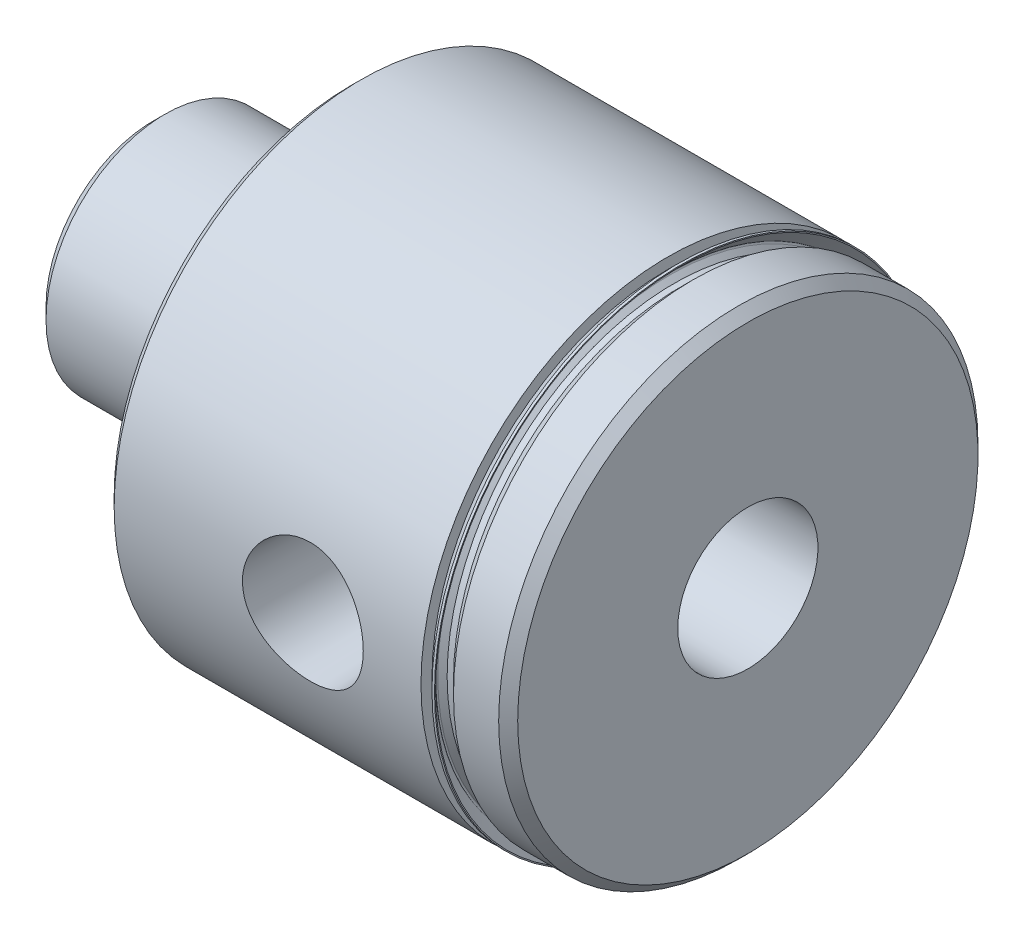
SolidWorks part; units mm, degrees
material "6061-T6 (SS)"
ref_plane "Front Plane" through (0, 0, 0) normal (0, 0, 1) x (1, 0, 0)
ref_plane "Top Plane" through (0, 0, 0) normal (0, 1, 0) x (1, 0, 0)
ref_plane "Right Plane" through (0, 0, 0) normal (1, 0, 0) x (0, 0, -1)
sketch "Sketch1" plane through (0, 0, 0) normal (0, 0, 1) x (1, 0, 0)
  line L0 (0, 0) -> (0, 8.589)
  line L1 (0, 8.589) -> (0.936, 9.525)
  line L2 (0.936, 9.525) -> (9.31, 9.525)
  line L3 (9.31, 9.525) -> (10.2623, 8.6108)
  line L4 (11.0363, 8.2995) -> (12.3698, 8.2995)
  line L5 (13.4874, 9.417) -> (13.4874, 9.4932)
  line L6 (13.4874, 9.4932) -> (15.875, 9.4932)
  line L7 (15.875, 9.4932) -> (15.875, 0)
  line L8 (15.875, 0) -> (0, 0)
  line L9 (15.875, 0) -> (0, 0) construction
  arc A0 (10.2623, 8.6108) -> (11.0363, 8.2995) centre (11.0363, 9.417) ccw
  arc A1 (12.3698, 8.2995) -> (13.4874, 9.417) centre (12.3698, 9.4171) ccw
revolve "Revolve1" add sketch "Sketch1" angle 360 about L9 reverse direction yes
cosmetic thread "Cosmetic Thread1" parameters "D1"=10.246, "D2"=17.178
sketch "Sketch2" plane through (0, 0, 0) normal (0, 0, 1) x (1, 0, 0)
  line L0 (15.875, 0) -> (15.875, 19.0055)
  line L1 (15.875, 19.0055) -> (16.637, 19.7676)
  line L2 (16.637, 19.7676) -> (41.2115, 19.7676)
  line L3 (41.2115, 19.7676) -> (41.2115, 18.1801)
  line L4 (41.2115, 18.1801) -> (42.2275, 18.1801)
  line L5 (42.2275, 18.1801) -> (43.2435, 19.196)
  line L6 (43.2435, 19.196) -> (46.863, 19.196)
  line L7 (46.863, 19.196) -> (47.625, 18.434)
  line L8 (47.625, 18.434) -> (47.625, 0)
  line L9 (47.625, 0) -> (15.875, 0)
  line L10 (47.625, 0) -> (15.875, 0) construction
revolve "Revolve2" add sketch "Sketch2" angle 360 about L10 reverse direction yes
sketch "Sketch3" plane through (0, 0, 0) normal (0, 0, 1) x (1, 0, 0)
  line L0 (0, 0) -> (0, 6.3754)
  line L1 (0, 6.3754) -> (0.762, 5.6134)
  line L2 (0.762, 5.6134) -> (47.625, 5.6134)
  line L3 (47.625, 5.6134) -> (47.625, 0)
  line L4 (47.625, 0) -> (0, 0)
  line L5 (47.625, 0) -> (0, 0) construction
revolve "Cut-Revolve1" cut sketch "Sketch3" angle 360 about L5 reverse direction yes
ref_plane "Plane1" through (25.527, 0, 0) normal (1, 0, 0) x (0, 0, -1)
ref_plane "Plane2" through (25.527, 0, 0) normal (1, 0, 0) x (0, 0, -1)
ref_plane "Plane3" through (0, 0, 0) normal (0, -0.7071, 0.7071) x (1, 0, 0)
ref_plane "Plane4" through (3.1242, 0, 0) normal (1, 0, 0) x (0, 0, -1)
ref_plane "Plane5" through (41.275, 0, 0) normal (1, 0, 0) x (0, 0, -1)
ref_plane "Plane6" through (15.875, 0, 0) normal (1, 0, 0) x (0, 0, -1)
ref_plane "Plane7" through (41.275, 0, 0) normal (1, 0, 0) x (0, 0, -1)
sketch "Sketch4" plane through (0, 0, 0) normal (0, 1, 0) x (1, 0, 0)
  line L0 (31.75, 0) -> (34.925, 0)
  line L1 (34.925, 0) -> (34.925, -7.7681)
  line L2 (34.925, -7.7681) -> (36.2564, -9.0996)
  line L3 (36.2564, -9.0996) -> (36.5895, -19.7676)
  line L4 (36.5895, -19.7676) -> (31.75, -19.7676)
  line L5 (31.75, -19.7676) -> (31.75, 0)
  line L6 (31.75, -19.7676) -> (31.75, 0) construction
revolve "Cut-Revolve2" cut sketch "Sketch4" angle 360 about L6 reverse direction yes
cosmetic thread "Cosmetic Thread2" parameters "D1"=6.4008, "D2"=10.287
sketch "Sketch5" plane through (0, 0, 0) normal (0, 0, 1) x (1, 0, 0)
  line L0 (41.2115, 18.8883) -> (41.2115, 17.9261)
  line L1 (41.2115, 17.9261) -> (42.2275, 17.9261)
  line L2 (42.2275, 17.9261) -> (42.2275, 18.1801)
  line L3 (42.2275, 18.1801) -> (41.7195, 18.1801)
  line L4 (41.7195, 18.1801) -> (41.3449, 18.5547)
  line L5 (41.3449, 18.7343) -> (42.294, 19.6834)
  line L6 (42.294, 19.6834) -> (42.294, 19.7676)
  line L7 (42.294, 19.7676) -> (42.0908, 19.7676)
  line L8 (42.0908, 19.7676) -> (41.2115, 18.8883)
  line L9 (42.2275, 0) -> (41.2115, 0) construction
  arc A0 (41.3449, 18.5547) -> (41.3449, 18.7343) centre (41.4347, 18.6445) cw
revolve "Revolve3" add sketch "Sketch5" angle 360 about L9 reverse direction yes
ref_plane "Plane8" through (42.2275, 0, 0) normal (1, 0, 0) x (0, 0, -1)
ref_plane "Plane9" through (15.875, 0, 0) normal (1, 0, 0) x (0, 0, -1)
ref_plane "Plane10" through (13.4874, 0, 0) normal (1, 0, 0) x (0, 0, -1)
ref_plane "Plane11" through (0, 22.225, 0) normal (0, 1, 0) x (1, 0, 0)
ref_plane "Plane12" through (0, -22.225, 0) normal (0, 1, 0) x (1, 0, 0)
ref_plane "Plane13" through (15.875, 0, 0) normal (1, 0, 0) x (0, 0, -1)
ref_plane "Plane14" through (0, 0, 0) normal (0, 0, 1) x (1, 0, 0)
ref_plane "Plane15" through (0, 0, 0) normal (0, 1, 0) x (1, 0, 0)
ref_plane "Plane16" through (0, 0, 0) normal (0, 1, 0) x (1, 0, 0)
ref_plane "Plane17" through (0, 14.2875, 0) normal (0, 1, 0) x (1, 0, 0)
ref_plane "Plane18" through (0, 0, 0) normal (1, 0, 0) x (0, 0, -1)
ref_plane "dp1 XY" through (0, 0, 0) normal (0, 0, 1) x (1, 0, 0)
ref_plane "dp1 XZ" through (0, 9.4932, 0) normal (0, -1, 0) x (-1, 0, 0)
ref_plane "dp1 YZ" through (15.875, 0, 0) normal (1, 0, 0) x (0, 0, -1)
ref_axis "dp1 X" through (-80.9, 9.4932, 0) along (1, 0, 0)
ref_axis "dp1 Y" through (15.875, -50, 0) along (0, 1, 0)
ref_axis "dp1 Z" through (15.875, 9.4932, 80.9) along (0, 0, -1)
sketch3d "dp1"
  point P0 (15.875, 9.4932, 0)
ref_plane "dp2 XY" through (0, 0, 0) normal (0, 0, 1) x (1, 0, 0)
ref_plane "dp2 XZ" through (0, -9.4932, 0) normal (0, -1, 0) x (-1, 0, 0)
ref_plane "dp2 YZ" through (15.875, 0, 0) normal (1, 0, 0) x (0, 0, -1)
ref_axis "dp2 X" through (-80.9, -9.4932, 0) along (1, 0, 0)
ref_axis "dp2 Y" through (15.875, -50, 0) along (0, 1, 0)
ref_axis "dp2 Z" through (15.875, -9.4932, 80.9) along (0, 0, -1)
sketch3d "dp2"
  point P0 (15.875, -9.4932, 0)
ref_plane "port XY" through (0, 0, 0) normal (0, 0, 1) x (1, 0, 0)
ref_plane "port XZ" through (0, 0, 0) normal (0, -1, 0) x (-1, 0, 0)
ref_plane "port YZ" through (31.75, 0, 0) normal (1, 0, 0) x (0, 0, -1)
ref_axis "port X" through (-80.9, 0, 0) along (1, 0, 0)
ref_axis "port Y" through (31.75, -50, 0) along (0, 1, 0)
ref_axis "port Z" through (31.75, 0, 80.9) along (0, 0, -1)
sketch3d "port"
  point P0 (31.75, 0, 0)
ref_plane "rod_guide XY" through (0, 0, 0) normal (1, 0, 0) x (0, 0, -1)
ref_plane "rod_guide XZ" through (0, 0, 0) normal (0, -1, 0) x (-1, 0, 0)
ref_plane "rod_guide YZ" through (0, 0, 0) normal (0, 0, -1) x (-1, 0, 0)
ref_axis "rod_guide X" through (0, 0, 80.9) along (0, 0, -1)
ref_axis "rod_guide Y" through (0, -50, 0) along (0, 1, 0)
ref_axis "rod_guide Z" through (80.9, 0, 0) along (-1, 0, 0)
sketch3d "rod_guide"
  point P0 (0, 0, 0)
ref_plane "s1 XY" through (0, 0, 0) normal (0, 0, 1) x (1, 0, 0)
ref_plane "s1 XZ" through (0, 0, 0) normal (0, -1, 0) x (-1, 0, 0)
ref_plane "s1 YZ" through (13.4874, 0, 0) normal (1, 0, 0) x (0, 0, -1)
ref_axis "s1 X" through (-80.9, 0, 0) along (1, 0, 0)
ref_axis "s1 Y" through (13.4874, -50, 0) along (0, 1, 0)
ref_axis "s1 Z" through (13.4874, 0, 80.9) along (0, 0, -1)
sketch3d "s1"
  point P0 (13.4874, 0, 0)
ref_plane "s2 XY" through (0, 0, 0) normal (0, 0, 1) x (1, 0, 0)
ref_plane "s2 XZ" through (0, 0, 0) normal (0, -1, 0) x (-1, 0, 0)
ref_plane "s2 YZ" through (15.875, 0, 0) normal (1, 0, 0) x (0, 0, -1)
ref_axis "s2 X" through (-80.9, 0, 0) along (1, 0, 0)
ref_axis "s2 Y" through (15.875, -50, 0) along (0, 1, 0)
ref_axis "s2 Z" through (15.875, 0, 80.9) along (0, 0, -1)
sketch3d "s2"
  point P0 (15.875, 0, 0)
ref_plane "t1 XY" through (15.875, 0, 0) normal (1, 0, 0) x (0, 0, -1)
ref_plane "t1 XZ" through (0, 0, 0) normal (0, -1, 0) x (-1, 0, 0)
ref_plane "t1 YZ" through (0, 0, 0) normal (0, 0, -1) x (-1, 0, 0)
ref_axis "t1 X" through (15.875, 0, 80.9) along (0, 0, -1)
ref_axis "t1 Y" through (15.875, -50, 0) along (0, 1, 0)
ref_axis "t1 Z" through (80.9, 0, 0) along (-1, 0, 0)
sketch3d "t1"
  point P0 (15.875, 0, 0)
ref_plane "t111 XY" through (15.875, 0, 0) normal (1, 0, 0) x (0, 0, -1)
ref_plane "t111 XZ" through (0, 0, 0) normal (0, -1, 0) x (-1, 0, 0)
ref_plane "t111 YZ" through (0, 0, 0) normal (0, 0, -1) x (-1, 0, 0)
ref_axis "t111 X" through (15.875, 0, 80.9) along (0, 0, -1)
ref_axis "t111 Y" through (15.875, -50, 0) along (0, 1, 0)
ref_axis "t111 Z" through (80.9, 0, 0) along (-1, 0, 0)
sketch3d "t111"
  point P0 (15.875, 0, 0)
ref_plane "to_foot_bracket XY" through (15.875, 0, 0) normal (1, 0, 0) x (0, 0, -1)
ref_plane "to_foot_bracket XZ" through (0, 0, 0) normal (0, -1, 0) x (-1, 0, 0)
ref_plane "to_foot_bracket YZ" through (0, 0, 0) normal (0, 0, -1) x (-1, 0, 0)
ref_axis "to_foot_bracket X" through (15.875, 0, 80.9) along (0, 0, -1)
ref_axis "to_foot_bracket Y" through (15.875, -50, 0) along (0, 1, 0)
ref_axis "to_foot_bracket Z" through (80.9, 0, 0) along (-1, 0, 0)
sketch3d "to_foot_bracket"
  point P0 (15.875, 0, 0)
ref_plane "to_nut XY" through (13.4874, 0, 0) normal (1, 0, 0) x (0, 0, -1)
ref_plane "to_nut XZ" through (0, 0, 0) normal (0, -1, 0) x (-1, 0, 0)
ref_plane "to_nut YZ" through (0, 0, 0) normal (0, 0, -1) x (-1, 0, 0)
ref_axis "to_nut X" through (13.4874, 0, 80.9) along (0, 0, -1)
ref_axis "to_nut Y" through (13.4874, -50, 0) along (0, 1, 0)
ref_axis "to_nut Z" through (80.9, 0, 0) along (-1, 0, 0)
sketch3d "to_nut"
  point P0 (13.4874, 0, 0)
ref_plane "to_rod XY" through (0, 0, 0) normal (1, 0, 0) x (0, 0, -1)
ref_plane "to_rod XZ" through (0, 0, 0) normal (0, -1, 0) x (-1, 0, 0)
ref_plane "to_rod YZ" through (0, 0, 0) normal (0, 0, -1) x (-1, 0, 0)
ref_axis "to_rod X" through (0, 0, 80.9) along (0, 0, -1)
ref_axis "to_rod Y" through (0, -50, 0) along (0, 1, 0)
ref_axis "to_rod Z" through (80.9, 0, 0) along (-1, 0, 0)
sketch3d "to_rod"
  point P0 (0, 0, 0)
ref_plane "to_screw XY" through (0, 14.2875, 0) normal (0, 1, 0) x (1, 0, 0)
ref_plane "to_screw XZ" through (0, 0, -10.0711) normal (0, 0, 1) x (1, 0, 0)
ref_plane "to_screw YZ" through (31.75, 0, 0) normal (1, 0, 0) x (0, 0, -1)
ref_axis "to_screw X" through (-80.9, 14.2875, -10.0711) along (1, 0, 0)
ref_axis "to_screw Y" through (31.75, 14.2875, 50) along (0, 0, -1)
ref_axis "to_screw Z" through (31.75, 50, -10.0711) along (0, -1, 0)
sketch3d "to_screw"
  point P0 (31.75, 14.2875, -10.0711)
ref_plane "to_trunnion_brackets XY" through (0, 0, 0) normal (0, 1, 0) x (1, 0, 0)
ref_plane "to_trunnion_brackets XZ" through (0, 0, 0) normal (0, 0, 1) x (1, 0, 0)
ref_plane "to_trunnion_brackets YZ" through (26.9494, 0, 0) normal (1, 0, 0) x (0, 0, -1)
ref_axis "to_trunnion_brackets X" through (-80.9, 0, 0) along (1, 0, 0)
ref_axis "to_trunnion_brackets Y" through (26.9494, 0, 50) along (0, 0, -1)
ref_axis "to_trunnion_brackets Z" through (26.9494, 50, 0) along (0, -1, 0)
sketch3d "to_trunnion_brackets"
  point P0 (26.9494, 0, 0)
ref_plane "to_trunnion_brackets1 XY" through (0, 22.225, 0) normal (0, 1, 0) x (1, 0, 0)
ref_plane "to_trunnion_brackets1 XZ" through (0, 0, 0) normal (0, 0, 1) x (1, 0, 0)
ref_plane "to_trunnion_brackets1 YZ" through (26.9494, 0, 0) normal (1, 0, 0) x (0, 0, -1)
ref_axis "to_trunnion_brackets1 X" through (-80.9, 22.225, 0) along (1, 0, 0)
ref_axis "to_trunnion_brackets1 Y" through (26.9494, 22.225, 50) along (0, 0, -1)
ref_axis "to_trunnion_brackets1 Z" through (26.9494, 50, 0) along (0, -1, 0)
sketch3d "to_trunnion_brackets1"
  point P0 (26.9494, 22.225, 0)
ref_plane "to_trunnion_brackets2 XY" through (0, -22.225, 0) normal (0, 1, 0) x (1, 0, 0)
ref_plane "to_trunnion_brackets2 XZ" through (0, 0, 0) normal (0, 0, 1) x (1, 0, 0)
ref_plane "to_trunnion_brackets2 YZ" through (26.9494, 0, 0) normal (1, 0, 0) x (0, 0, -1)
ref_axis "to_trunnion_brackets2 X" through (-80.9, -22.225, 0) along (1, 0, 0)
ref_axis "to_trunnion_brackets2 Y" through (26.9494, -22.225, 50) along (0, 0, -1)
ref_axis "to_trunnion_brackets2 Z" through (26.9494, 50, 0) along (0, -1, 0)
sketch3d "to_trunnion_brackets2"
  point P0 (26.9494, -22.225, 0)
ref_plane "to_tube XY" through (42.2275, 0, 0) normal (1, 0, 0) x (0, 0, -1)
ref_plane "to_tube XZ" through (0, 0, 0) normal (0, -1, 0) x (-1, 0, 0)
ref_plane "to_tube YZ" through (0, 0, 0) normal (0, 0, -1) x (-1, 0, 0)
ref_axis "to_tube X" through (42.2275, 0, 80.9) along (0, 0, -1)
ref_axis "to_tube Y" through (42.2275, -50, 0) along (0, 1, 0)
ref_axis "to_tube Z" through (80.9, 0, 0) along (-1, 0, 0)
sketch3d "to_tube"
  point P0 (42.2275, 0, 0)
